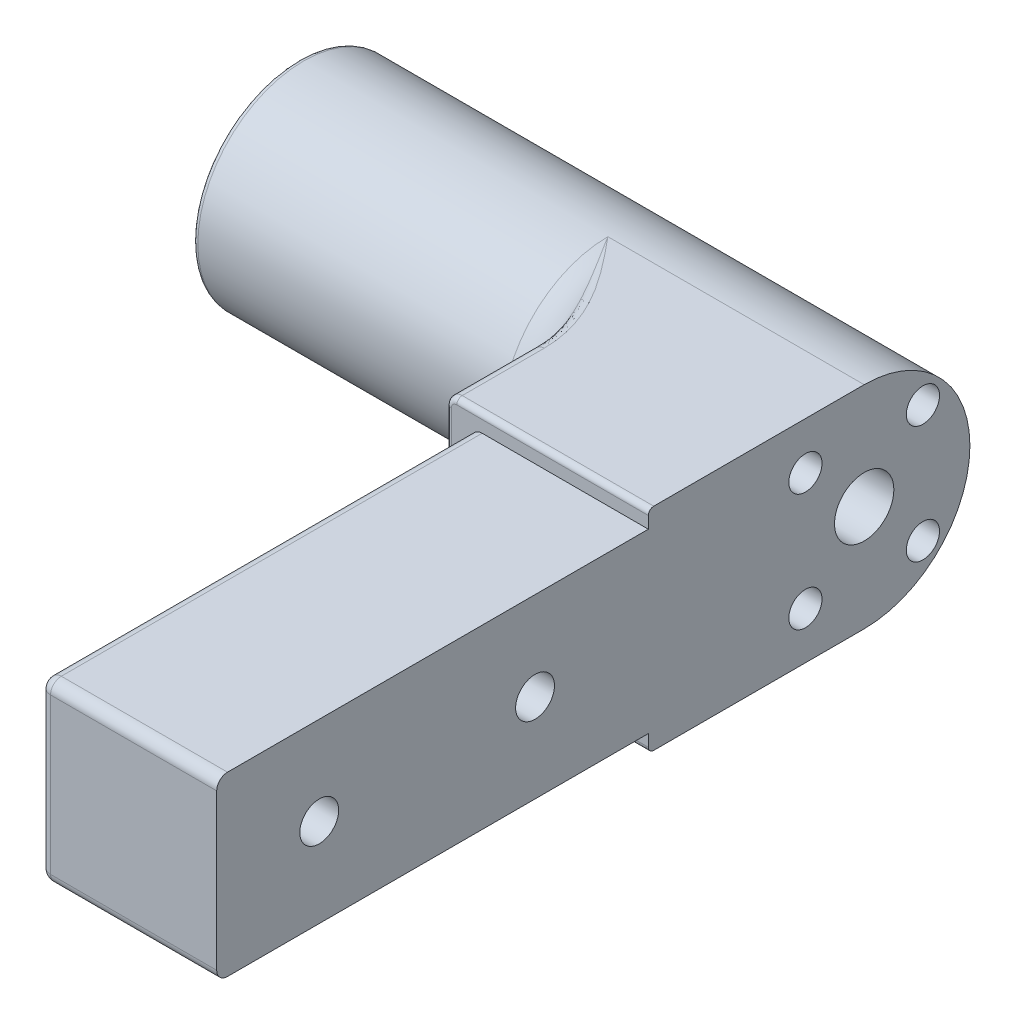
SolidWorks part; units mm, degrees
ref_plane "Front Plane" through (0, 0, 0) normal (0, 0, 1) x (1, 0, 0)
ref_plane "Top Plane" through (0, 0, 0) normal (0, 1, 0) x (1, 0, 0)
ref_plane "Right Plane" through (0, 0, 0) normal (1, 0, 0) x (0, 0, -1)
sketch "Sketch1" plane through (0, 0, 0) normal (1, 0, 0) x (0, 0, -1)
  line L0 (0, 0) -> (-25.4, 0) construction
  line L1 (0, 0) -> (6.9148, 6.9148) construction
  line L8 (-25.4, -12.446) -> (0, -12.446)
  line L9 (-25.4, -12.446) -> (-25.4, 12.446)
  line L10 (-25.4, 12.446) -> (0, 12.446)
  line L11 (0, -12.446) -> (0, 12.446)
  line L12 (-25.4, -12.446) -> (0, 12.446) construction
  line L13 (-25.4, 12.446) -> (0, -12.446) construction
  circle A0 centre (0, 0) radius 12.446
  circle A1 centre (6.9148, 6.9148) radius 1.9558
  circle A5 centre (9.779, 0) radius 1.9558 construction
  circle A6 centre (6.9148, -6.9148) radius 1.9558
  circle A7 centre (0, -9.779) radius 1.9558 construction
  circle A8 centre (-6.9148, -6.9148) radius 1.9558
  circle A9 centre (-9.779, 0) radius 1.9558 construction
  circle A10 centre (-6.9148, 6.9148) radius 1.9558
  circle A11 centre (0, 9.779) radius 1.9558 construction
  circle A12 centre (0, 0) radius 3.4925
  point P4 (-12.7, 0)
  point P5 (-28.4742, 0)
  point P7 (-25.4, 0)
  point P34 (0, 0)
  dimension "D1" = 24.892
  dimension "D5" = 3.9116
  dimension "D9" = 6.985
  dimension "D3" = 25.4
  dimension "D6" = 9.779
  dimension "D8" = 45
  dimension "D7" = 8
extrude "Boss-Extrude1" add sketch "Sketch1" along normal blind 11.1125 and the other way blind 12.7 contours A12 L11 A7 A0 A11 A6 A5 A1 | A12 L11 A11 A0 A10 A8 A7 | A0 L9 | A0 L10 L9 | A10 A0 A8 A9 | A0 L9 L8 region at (0, 0, 17.3406) region at (0, 0, 5.45) region at (0, 0, -5.45)
sketch "Sketch2" plane through (0, 0, 25.4) normal (0, 0, 1) x (1, 0, 0)
  line L0 (11.1125, -12.446) -> (11.1125, 12.446) construction
  line L5 (11.1125, -10.414) -> (-9.7155, -10.414)
  line L6 (11.1125, -10.414) -> (11.1125, 10.414)
  line L7 (11.1125, 10.414) -> (-9.7155, 10.414)
  line L8 (-9.7155, -10.414) -> (-9.7155, 10.414)
  line L9 (-12.7, -12.446) -> (-12.7, 12.446) construction
  point P0 (0, 0)
  point P8 (-9.7155, 0)
  point P9 (-12.7, 0)
  dimension "D1" = 20.828
  dimension "D2" = 20.828
extrude "Boss-Extrude2" add sketch "Sketch2" along normal blind 50.8
sketch "Sketch3" plane through (-12.7, 0, 0) normal (-1, 0, 0) x (0, 0, 1)
  circle A0 centre (0, 0) radius 12.446
  arc A1 (0, 12.446) -> (0, -12.446) centre (0, 0) ccw construction
  circle A2 centre (0, 0) radius 3.4925 construction
  circle A3 centre (-6.9148, -6.9148) radius 1.9558 construction
  circle A5 centre (-6.9148, 6.9148) radius 1.9558 construction
  circle A7 centre (6.9148, 6.9148) radius 1.9558 construction
  circle A9 centre (6.9148, -6.9148) radius 1.9558 construction
  circle A11 centre (0, 0) radius 3.4925
  circle A12 centre (-6.9148, -6.9148) radius 1.9558
  circle A14 centre (-6.9148, 6.9148) radius 1.9558
  circle A16 centre (6.9148, 6.9148) radius 1.9558
  circle A18 centre (6.9148, -6.9148) radius 1.9558
extrude "Boss-Extrude3" add sketch "Sketch3" along normal blind 42.799
sketch "Sketch6" plane through (-9.7155, 0, 0) normal (-1, 0, 0) x (0, 0, 1)
  line L0 (76.2, 0) -> (25.4, 0) construction
  line L1 (76.2, 10.414) -> (76.2, -10.414) construction
  line L2 (25.4, 10.414) -> (25.4, -10.414) construction
  circle A0 centre (38.735, 0) radius 2.286
  circle A1 centre (64.135, 0) radius 2.286
  circle A2 centre (38.735, 0) radius 2.1828 construction
  circle A3 centre (38.735, 0) radius 2.1828 construction
  circle A4 centre (64.135, 0) radius 2.1828 construction
  circle A5 centre (64.135, 0) radius 2.1828 construction
  dimension "D2" = 4.572
extrude "Cut-Extrude2" cut sketch "Sketch6" against normal up to surface (20.828 mm away) up to face at (11.1125, 0, -3.4925)
fillet "Fillet1" radius 6.35 1 edges at (-12.7, 0, 12.446)
fillet "Fillet2" radius 1.27 9 edges at (-12.7, -12.446, 19.7425) (-12.7, 12.446, 19.7425) (-9.7155, -10.414, 50.8) (-13.4496, -12.446, 9.738) (-13.4496, 12.446, 9.738) (-9.7155, 0, 76.2) (0.6985, -10.414, 76.2) (0.6985, 10.414, 76.2) (-9.7155, 10.414, 50.8)
fillet "Fillet3" radius 0.635 6 edges at (-0.1588, -12.446, 25.4) (-12.328, -12.074, 25.4) (-0.1588, 12.446, 25.4) (-12.328, 12.074, 25.4) (-12.7, 0, 25.4) (-55.499, 0, 12.446)
